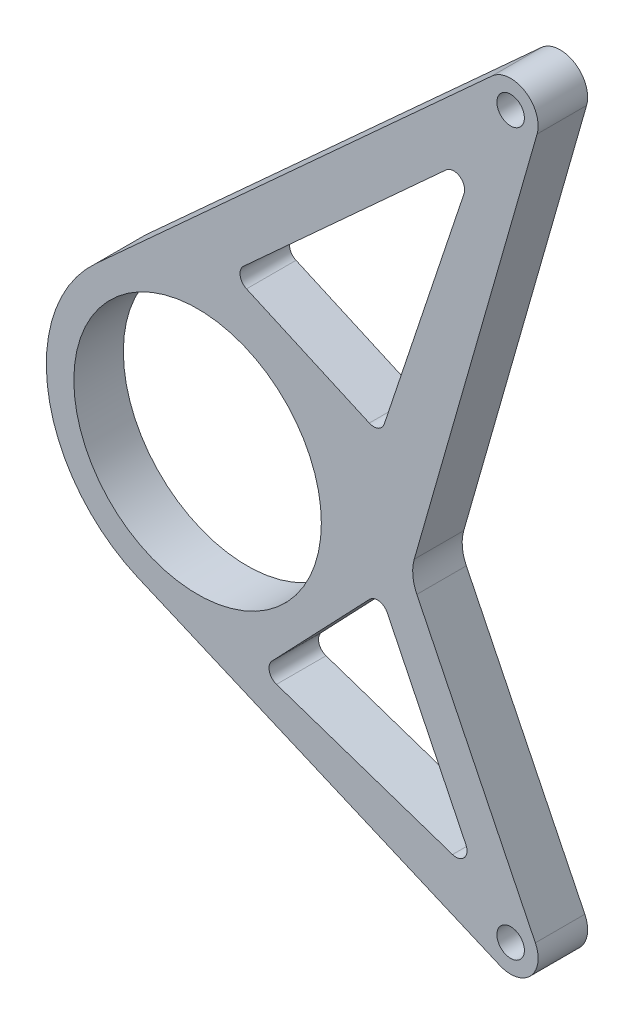
SolidWorks part; units mm, degrees
material "1023 Carbon Steel Sheet (SS)"
ref_plane "Front Plane" through (0, 0, 0) normal (0, 0, 1) x (1, 0, 0)
ref_plane "Top Plane" through (0, 0, 0) normal (0, 1, 0) x (1, 0, 0)
ref_plane "Right Plane" through (0, 0, 0) normal (1, 0, 0) x (0, 0, -1)
sketch "Sketch2" plane through (0, 0, 0) normal (0, 0, 1) x (1, 0, 0)
  line L0 (-38.6653, 39.1784) -> (107.0992, 171.8423)
  line L1 (-21.6474, -50.5608) -> (109.8942, -106.8797)
  line L2 (122.8143, -93.2954) -> (79.7177, -5.1262)
  line L3 (78.7806, 5.486) -> (123.4448, 161.6976)
  line L4 (113.8301, 164.4467) -> (-141.4394, 164.4467) construction
  line L5 (113.8301, -97.6868) -> (-130.107, -97.6868) construction
  line L6 (0, 0) -> (113.8301, 164.4467) construction
  line L7 (0, 0) -> (113.8301, -97.6868) construction
  circle A0 centre (0, 0) radius 45
  arc A1 (-37.02, 40.6758) -> (-21.6474, -50.5608) centre (0, 0) ccw
  circle A2 centre (113.8301, 164.4467) radius 5
  arc A3 (123.4448, 161.6976) -> (107.0992, 171.8423) centre (113.8301, 164.4467) ccw
  arc A4 (109.8942, -106.8797) -> (122.8143, -93.2954) centre (113.8301, -97.6868) ccw
  circle A5 centre (113.8301, -97.6868) radius 5
  arc A6 (79.7177, -5.1262) -> (78.7806, 5.486) centre (93.0701, 1.4003) cw
  point P23 (77.2121, 0)
  dimension "D1" = 90
  dimension "D2" = 10
  dimension "D3" = 20
  dimension "D4" = 20
  dimension "D5" = 10
  dimension "D9" = 110
  dimension "D10" = 14.8621
  dimension "D6" = 200
  dimension "D7" = 55.309
  dimension "D8" = 150
extrude "Boss-Extrude2" add sketch "Sketch2" along normal blind 18 contours L2 A6 L3 A3 L0 A1 L1 A4 A0 A2 A5 region at (55.8052, 26.3176, 0)
sketch "Sketch3" plane through (0, 0, 18) normal (0, 0, 1) x (1, 0, 0)
  line L0 (17.7957, 60.1214) -> (62.4379, 40.1841)
  line L1 (67.8638, 42.5715) -> (96.9029, 129.6889)
  line L2 (90.4131, 133.9096) -> (16.7318, 66.7296)
  line L3 (27.0859, -52.4066) -> (62.4963, -15.2896)
  line L4 (68.9868, -16.2997) -> (97.5712, -75.0068)
  line L5 (92.6961, -80.5479) -> (28.7014, -58.9578)
  arc A0 (27.0859, -52.4066) -> (28.7014, -58.9578) centre (29.9801, -55.1677) ccw
  arc A1 (68.9868, -16.2997) -> (62.4963, -15.2896) centre (65.3905, -18.0507) ccw
  arc A2 (92.6961, -80.5479) -> (97.5712, -75.0068) centre (93.9748, -76.7578) ccw
  arc A3 (62.4379, 40.1841) -> (67.8638, 42.5715) centre (64.0691, 43.8365) ccw
  arc A4 (16.7318, 66.7296) -> (17.7957, 60.1214) centre (19.4269, 63.7738) ccw
  arc A5 (90.4131, 133.9096) -> (96.9029, 129.6889) centre (93.1082, 130.9538) cw
  dimension "D1" = 4
extrude "Cut-Extrude1" cut sketch "Sketch3" against normal up to surface (18 mm away) up to face at (45, 0, 0)
